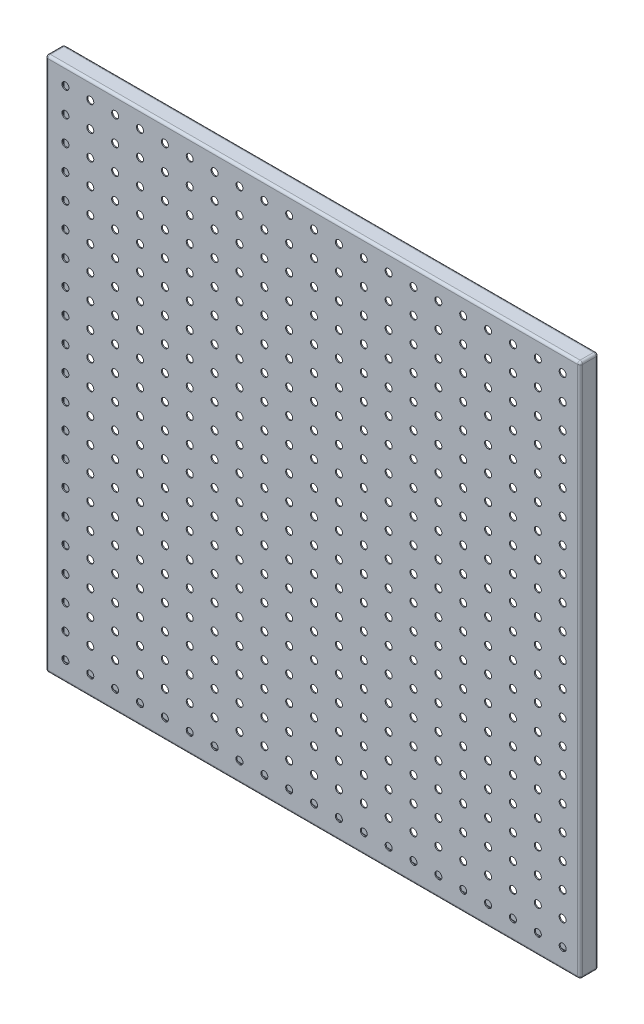
SolidWorks part; units mm, degrees
ref_plane "Front Plane" through (0, 0, 0) normal (0, 0, 1) x (1, 0, 0)
ref_plane "Top Plane" through (0, 0, 0) normal (0, 1, 0) x (1, 0, 0)
ref_plane "Right Plane" through (0, 0, 0) normal (1, 0, 0) x (0, 0, -1)
sketch "Sketch2" plane through (0, 0, 0) normal (0, 0, 1) x (1, 0, 0)
  line L1 (0, 0) -> (546.1, 0)
  line L2 (0, 0) -> (0, 546.1)
  line L3 (0, 546.1) -> (546.1, 546.1)
  line L4 (546.1, 0) -> (546.1, 546.1)
  dimension "D1" = 546.1
  dimension "D2" = 546.1
extrude "Boss-Extrude1" add sketch "Sketch2" along normal blind 1.016
sketch "Sketch3" plane through (0, 0, 1.016) normal (0, 0, 1) x (1, 0, 0)
  line L0 (0, 546.1) -> (0, 0) construction
  line L1 (0, 0) -> (546.1, 0) construction
  circle A0 centre (20.32, 20.32) radius 3.5719
  circle A1 centre (45.72, 20.32) radius 3.5719
  circle A2 centre (45.72, 45.72) radius 3.5719
  circle A3 centre (20.32, 45.72) radius 3.5719
  dimension "D1" = 7.1437
  dimension "D2" = 25.4
  dimension "D3" = 25.4
  dimension "D4" = 20.32
  dimension "D5" = 20.32
extrude "Cut-Extrude1" cut sketch "Sketch3" against normal through all
pattern_linear "LPattern1" count 11 spacing 50.8 along (0, 1, 0) count 11 spacing 50.8 along (1, 0, 0) of "Cut-Extrude1"
sketch "Sketch4" plane through (0, 546.1, 0) normal (0, 1, 0) x (1, 0, 0)
  line L0 (0, 0) -> (0, 17.78)
  line L1 (0, 17.78) -> (12.7, 17.78)
  line L2 (12.7, 17.78) -> (12.7, 16.764)
  line L3 (12.7, 16.764) -> (1.016, 16.764)
  line L4 (1.016, 16.764) -> (1.016, 0)
  line L5 (546.1, 0) -> (0, 0) construction
  line L6 (1.016, 0) -> (0, 0)
  line L7 (546.1, 0) -> (546.1, 17.78)
  line L8 (546.1, 17.78) -> (533.4, 17.78)
  line L9 (533.4, 17.78) -> (533.4, 16.764)
  line L10 (533.4, 16.764) -> (545.084, 16.764)
  line L11 (545.084, 16.764) -> (545.084, 0)
  line L12 (545.084, 0) -> (546.1, 0)
  point P12 (531.6831, 17.78)
  dimension "D1" = 1.016
  dimension "D2" = 1.016
  dimension "D3" = 1.016
  dimension "D4" = 17.78
  dimension "D5" = 12.7
extrude "Boss-Extrude2" add sketch "Sketch4" against normal blind 546.1
sketch "Sketch5" plane through (546.1, 0, 0) normal (1, 0, 0) x (0, 0, -1)
  line L0 (0, 546.1) -> (17.78, 546.1)
  line L1 (17.78, 546.1) -> (17.78, 533.4)
  line L2 (17.78, 0) -> (17.78, 546.1) construction
  line L3 (17.78, 533.4) -> (16.764, 533.4)
  line L4 (16.764, 533.4) -> (16.764, 545.084)
  line L5 (16.764, 545.084) -> (0, 545.084)
  line L6 (0, 545.084) -> (0, 546.1)
  line L7 (0, 0) -> (17.78, 0)
  line L8 (17.78, 0) -> (17.78, 12.7)
  line L9 (17.78, 12.7) -> (16.764, 12.7)
  line L10 (16.764, 12.7) -> (16.764, 1.016)
  line L11 (16.764, 1.016) -> (0, 1.016)
  line L12 (0, 1.016) -> (0, 0)
  dimension "D1" = 1.016
  dimension "D2" = 12.7
extrude "Boss-Extrude3" add sketch "Sketch5" against normal blind 546.1
fillet "Fillet1" radius 2.54 12 edges at (546.1, 273.05, -17.78) (273.05, 546.1, -17.78) (273.05, 0, -17.78) (546.1, 0, -8.382) (546.1, 546.1, -8.382) (0, 546.1, -8.382) (0, 273.05, -17.78) (273.05, 546.1, 1.016) (0, 273.05, 1.016) (273.05, 0, 1.016) (546.1, 273.05, 1.016) (0, 0, -8.382)
